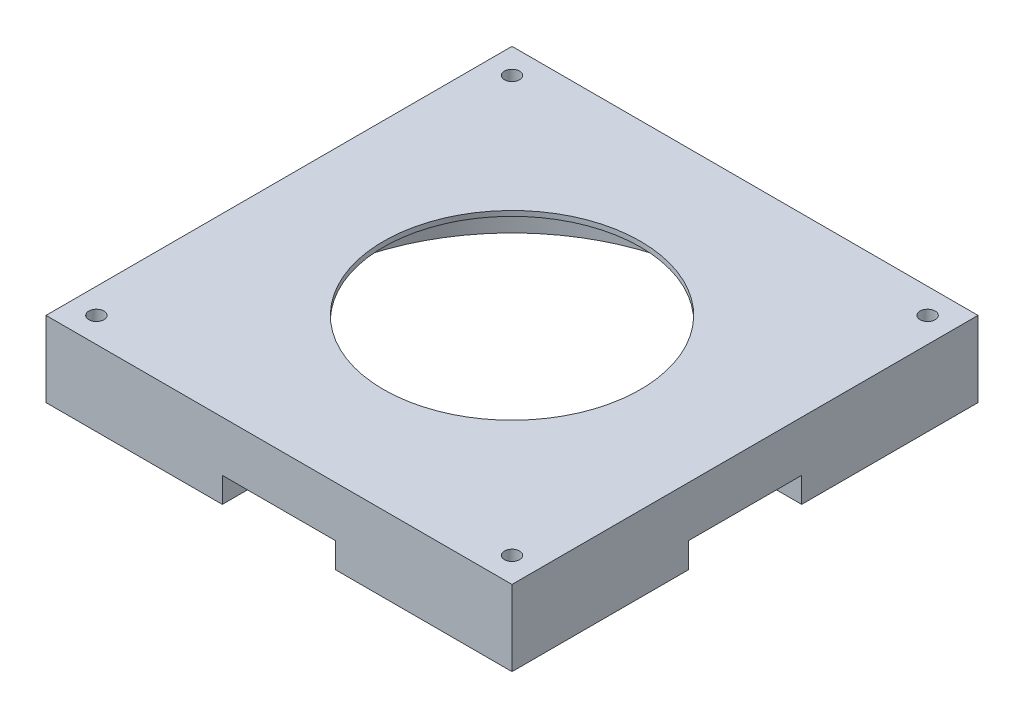
SolidWorks part; units mm, degrees
material "PE High Density"
ref_plane "Front Plane" through (0, 0, 0) normal (0, 0, 1) x (1, 0, 0)
ref_plane "Top Plane" through (0, 0, 0) normal (0, 1, 0) x (1, 0, 0)
ref_plane "Right Plane" through (0, 0, 0) normal (1, 0, 0) x (0, 0, -1)
sketch "Sketch1" plane through (0, 0, 0) normal (0, 0, 1) x (1, 0, 0)
  line L1 (51, -2) -> (82.5, -2)
  line L2 (82.5, -2) -> (82.5, -30)
  line L5 (82.5, -30) -> (85.5, -30)
  line L6 (85.5, -30) -> (85.5, 0)
  line L7 (85.5, 0) -> (51, 0)
  line L8 (51, -2) -> (51, 0)
  line L9 (0, 0) -> (51, 0) construction
  line L10 (0, 0) -> (0, -6.871) construction
  dimension "D1" = 3
  dimension "D3" = 2
  dimension "D5" = 30
  dimension "D6" = 82.5
  dimension "D7" = 51
revolve "Revolve1" add sketch "Sketch1" angle 360 about L10
sketch "Sketch2" plane through (0, -30, 0) normal (0, -1, 0) x (1, 0, 0)
  line L1 (-92.5, -92.5) -> (92.5, -92.5)
  line L2 (-92.5, -92.5) -> (-92.5, 92.5)
  line L3 (-92.5, 92.5) -> (92.5, 92.5)
  line L4 (92.5, -92.5) -> (92.5, 92.5)
  line L5 (-92.5, -92.5) -> (92.5, 92.5) construction
  line L6 (-92.5, 92.5) -> (92.5, -92.5) construction
  line L7 (-82.5, -82.5) -> (82.5, -82.5) construction
  line L8 (-82.5, -82.5) -> (-82.5, 82.5) construction
  line L9 (-82.5, 82.5) -> (82.5, 82.5) construction
  line L10 (82.5, -82.5) -> (82.5, 82.5) construction
  line L11 (-82.5, -82.5) -> (82.5, 82.5) construction
  line L12 (-82.5, 82.5) -> (82.5, -82.5) construction
  circle A0 centre (0, 0) radius 85.5
  circle A1 centre (0, 0) radius 85.5 construction
  circle A6 centre (-82.5, -82.5) radius 3
  circle A7 centre (82.5, -82.5) radius 3
  circle A8 centre (82.5, 82.5) radius 3
  circle A9 centre (-82.5, 82.5) radius 3
  dimension "D3" = 6
  dimension "D1" = 185
  dimension "D2" = 165
extrude "Boss-Extrude1" add sketch "Sketch2" against normal up to surface (30 mm away) up to face at (0, 0, 51)
sketch "Sketch3" plane through (-92.5, 0, 0) normal (-1, 0, 0) x (0, 0, 1)
  line L0 (92.5, -30) -> (-92.5, -30) construction
  line L1 (-22.5, -30) -> (22.5, -30)
  line L2 (-22.5, -30) -> (-22.5, -20)
  line L3 (-22.5, -20) -> (22.5, -20)
  line L4 (22.5, -30) -> (22.5, -20)
  line L5 (0, 0) -> (0, -20) construction
  line L6 (92.5, 0) -> (92.5, -30) construction
  dimension "D1" = 10
  dimension "D2" = 70
extrude "Cut-Extrude1" cut sketch "Sketch3" against normal through all
sketch "Sketch4" plane through (0, 0, -92.5) normal (0, 0, -1) x (-1, 0, 0)
  line L0 (92.5, -30) -> (-92.5, -30) construction
  line L1 (-22.5, -30) -> (22.5, -30)
  line L2 (-22.5, -30) -> (-22.5, -20)
  line L3 (-22.5, -20) -> (22.5, -20)
  line L4 (22.5, -30) -> (22.5, -20)
  line L5 (0, 0) -> (0, -20) construction
  line L6 (92.5, 0) -> (92.5, -30) construction
  dimension "D1" = 10
  dimension "D2" = 70
extrude "Cut-Extrude2" cut sketch "Sketch4" against normal through all
